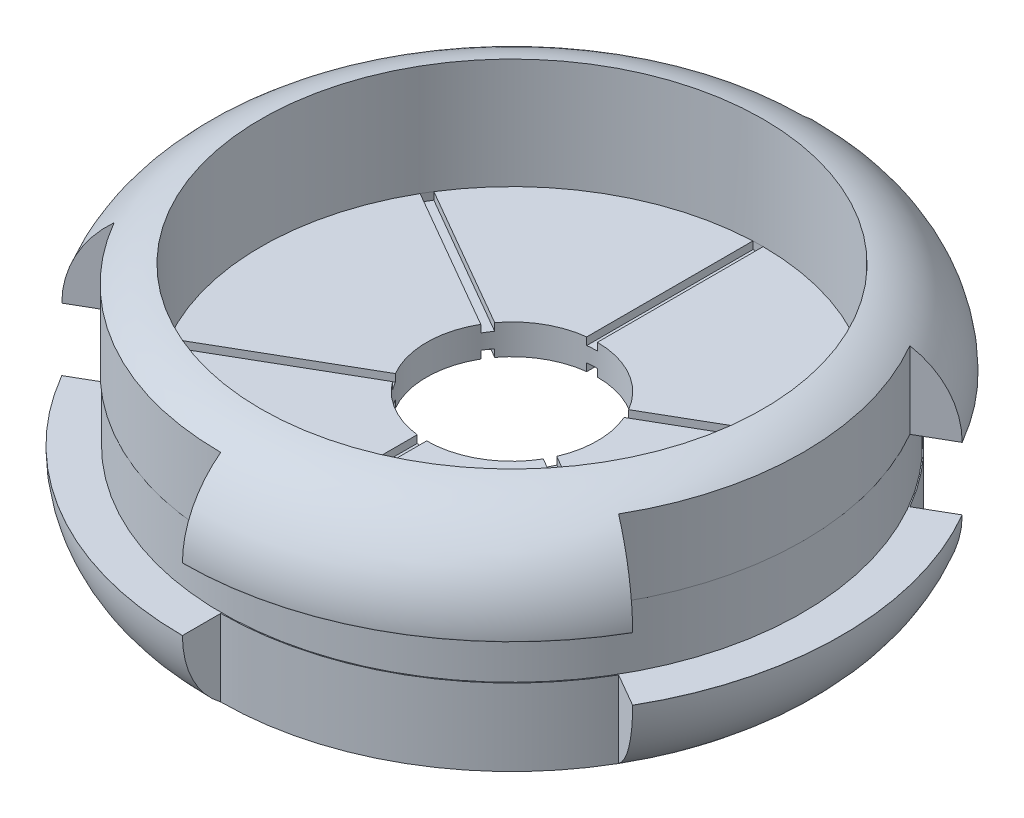
SolidWorks part; units mm, degrees
material "Rubber"
ref_plane "Front" through (0, 0, 0) normal (0, 0, 1) x (1, 0, 0)
ref_plane "Top" through (0, 0, 0) normal (0, 1, 0) x (1, 0, 0)
ref_plane "Right" through (0, 0, 0) normal (1, 0, 0) x (0, 0, -1)
sketch "Sketch1" plane through (0, 0, 0) normal (0, 0, 1) x (1, 0, 0)
  line L0 (-8.3344, 3.175) -> (8.3344, 3.175) construction
  line L1 (0, -3.175) -> (0, 3.175) construction
  line L2 (6.35, 0.7937) -> (6.35, -0.7937) construction
  line L3 (-8.3344, -3.175) -> (8.3344, -3.175) construction
  line L4 (-6.35, 0) -> (6.35, 0) construction
  dimension "D1" = 1.5875
  dimension "flange dia" = 16.6687
  dimension "oall ht" = 6.35
  dimension "for hole dia" = 12.7
sketch "Sketch2" plane through (0, 0, 0) normal (0, 0, 1) x (1, 0, 0)
  line L0 (8.3344, 3.175) -> (8.3344, 0.7938)
  line L1 (8.3344, 3.175) -> (6.35, 3.175)
  line L2 (-8.3344, 3.175) -> (8.3344, 3.175) construction
  line L3 (8.3344, 0.7938) -> (7.3422, 0.7937)
  line L4 (7.3422, 0.7937) -> (7.3422, -0.7937)
  line L5 (7.3422, -0.7937) -> (8.3344, -0.7938)
  line L6 (8.3344, -0.7938) -> (8.3344, -3.175)
  line L7 (8.3344, -3.175) -> (6.35, -3.175)
  line L8 (-8.3344, -3.175) -> (8.3344, -3.175) construction
  line L9 (6.35, -3.175) -> (6.35, 3.175)
  line L10 (6.35, 0.7937) -> (6.35, -0.7937) construction
  line L11 (-6.35, 0) -> (6.35, 0) construction
  point P8 (7.3422, 0)
  dimension "D1" = 0.9922
revolve "Revolve1" add sketch "Sketch2" angle 360 about L1
sketch "Sketch3" plane through (0, 0, 0) normal (0, 1, 0) x (1, 0, 0)
  circle A0 centre (0, 0) radius 6.35
  circle A1 centre (0, 0) radius 2.159
  dimension "D1" = 4.318
extrude "Boss-Extrude1" add sketch "Sketch3" along normal blind 0.381 and the other way blind 0.381
fillet "Fillet1" radius 2.413 2 edges at (0, -3.175, -8.3344) (0, 3.175, -8.3344)
ref_plane "Plane1" through (0, 3.175, 0) normal (0, -1, 0) x (1, 0, 0)
sketch "Sketch4" plane through (0, 3.175, 0) normal (0, -1, 0) x (1, 0, 0)
  line L0 (0, 0) -> (20.1244, 11.6188) construction
  line L1 (20.1244, 11.6188) -> (20.1244, -11.6188) construction
  line L2 (20.1244, -11.6188) -> (0, 0) construction
  line L4 (6.3791, 3.683) -> (7.2178, 4.1672)
  line L5 (6.3791, -3.683) -> (7.2178, -4.1672)
  line L6 (-8.3344, 0) -> (8.3344, 0) construction
  arc A0 (6.3791, 3.683) -> (6.3791, -3.683) centre (0, 0) cw
  circle A2 centre (0, 0) radius 8.3344 construction
  arc A3 (7.2178, 4.1672) -> (7.2178, -4.1672) centre (0, 0) cw
  circle A4 centre (0, 0) radius 8.3344 construction
  circle A5 centre (0, 0) radius 6.35 construction
  point P5 (6.35, 0)
  point P21 (7.366, 0)
  dimension "D1" = 1.016
  dimension "D2" = 20.1244
extrude "Cut-Extrude2" cut sketch "Sketch4" along normal up to surface (2.3813 mm away) up to face at (0, 0.7938, -8.3344)
pattern_circular "CirPattern1" count 3 over 360 about axis through (0, 3.175, 0) along (0, -1, 0) of "Cut-Extrude2"
ref_plane "Plane2" through (0, -3.175, 0) normal (0, -1, 0) x (1, 0, 0)
sketch "Sketch5" plane through (0, -3.175, 0) normal (0, -1, 0) x (1, 0, 0)
  line L0 (0, 0) -> (0, 23.2376) construction
  line L1 (0, 23.2376) -> (20.1244, 11.6188) construction
  line L2 (20.1244, 11.6188) -> (0, 0) construction
  line L3 (0, 0) -> (20.1244, 11.6188) construction
  line L4 (0, 8.3344) -> (0, 7.366)
  line L5 (7.2178, 4.1672) -> (6.3791, 3.683)
  line L6 (6.3791, 3.683) -> (7.2178, 4.1672) construction
  arc A0 (0, 7.366) -> (6.3791, 3.683) centre (0, 0) cw
  arc A1 (0, 8.3344) -> (7.2178, 4.1672) centre (0, 0) cw
  arc A2 (6.3791, -3.683) -> (6.3791, 3.683) centre (0, 0) ccw construction
  arc A3 (7.2178, -4.1672) -> (7.2178, 4.1672) centre (0, 0) ccw construction
extrude "Cut-Extrude3" cut sketch "Sketch5" against normal up to vertex (2.3813 mm away) up to point (6.35, -0.7937, 0)
pattern_circular "CirPattern2" count 3 over 360 about axis through (0, -3.175, 0) along (0, -1, 0) of "Cut-Extrude3"
sketch "Sketch6" plane through (0, 0.381, 0) normal (0, 1, 0) x (1, 0, 0)
  line L0 (0, 0) -> (5.4993, 3.175)
  line L1 (20.1244, 11.6188) -> (0, 0) construction
  line L2 (0, 0) -> (20.1244, -11.6188) construction
  line L3 (5.4993, -3.175) -> (0, 0)
  line L4 (5.6263, -2.955) -> (0.508, 0)
  line L5 (0.508, 0) -> (5.6263, 2.955)
  line L6 (5.4993, -3.175) -> (5.6263, -2.955)
  line L7 (5.4993, 3.175) -> (5.6263, 2.955)
  circle A0 centre (0, 0) radius 6.35 construction
  circle A1 centre (0, 0) radius 6.35 construction
  dimension "D1" = 0.254
extrude "Cut-Extrude4" cut sketch "Sketch6" against normal blind 0.1905
pattern_circular "CirPattern3" count 3 over 360 about axis through (0, 3.175, 0) along (0, -1, 0) of "Cut-Extrude4"
mirror "Mirror1" about plane through (0, 0, 0) normal (0, 1, 0) of "CirPattern3"
equation "\"D1@Sketch2\"=(\"flange dia@Sketch1\"-\"for hole dia@Sketch1\")/4"
